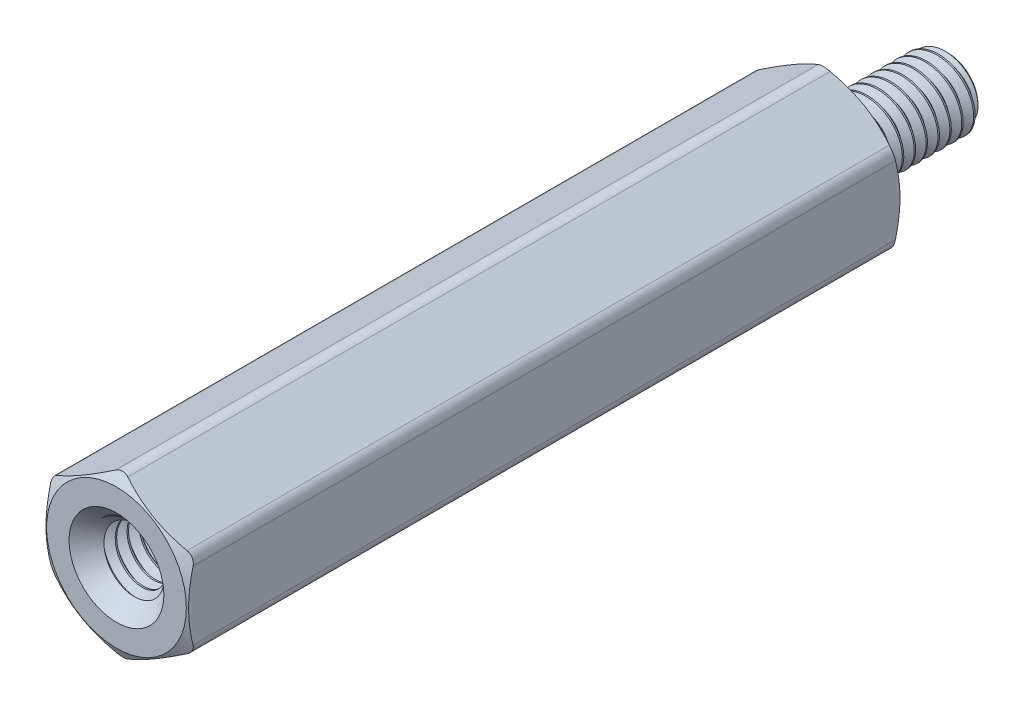
SolidWorks part; units mm, degrees
ref_plane "Front Plane" through (0, 0, 0) normal (0, 0, 1) x (1, 0, 0)
ref_plane "Top Plane" through (0, 0, 0) normal (0, 1, 0) x (1, 0, 0)
ref_plane "Right Plane" through (0, 0, 0) normal (1, 0, 0) x (0, 0, -1)
sketch "Sketch1" plane through (0, 0, 0) normal (0, 0, 1) x (1, 0, 0)
  line L1 (3, 1.7321) -> (0, 3.4641)
  line L2 (0, 3.4641) -> (-3, 1.7321)
  line L3 (-3, 1.7321) -> (-3, -1.7321)
  line L4 (-3, -1.7321) -> (0, -3.4641)
  line L5 (0, -3.4641) -> (3, -1.7321)
  line L6 (3, -1.7321) -> (3, 1.7321)
  circle A0 centre (0, 0) radius 3 construction
  point P10 (0, -3)
  dimension "Hex Size" = 6
sketch "Sketch2" plane through (0, 0, 0) normal (1, 0, 0) x (0, 0, -1)
  line L0 (5, 0) -> (-30, 0) construction
  line L2 (0, 1.5) -> (0, -1.5) construction
  line L3 (-23.6, 1.5) -> (-23.6, -1.5) construction
  line L4 (-30.4687, 1.5541) -> (-30.2187, 1.1211) construction
  line L5 (-30.2187, 1.1211) -> (-29.9687, 1.5541) construction
  line L6 (-29.9687, 1.5541) -> (-30.4687, 1.5541) construction
  line L7 (-30.4375, 1.5) -> (-30, 1.5) construction
  line L8 (-30.25, 1.1752) -> (-30.1875, 1.1752) construction
  line L9 (-30.2187, 1.1752) -> (-30.2187, 1.1211) construction
  line L10 (-30.2187, 1.5) -> (-30.2187, 1.5541) construction
  line L11 (4.9687, 1.5541) -> (5.4687, 1.5541) construction
  line L12 (5.4687, 1.5541) -> (5.2187, 1.1211) construction
  line L13 (5.2187, 1.1211) -> (4.9687, 1.5541) construction
  line L14 (5, 1.5) -> (5.4375, 1.5) construction
  line L15 (5.1875, 1.1752) -> (5.25, 1.1752) construction
  line L16 (5.2187, 1.1752) -> (5.2187, 1.1211) construction
  line L17 (5.2187, 1.5) -> (5.2187, 1.5541) construction
  line L18 (0, 3.4641) -> (-30, 3.4641) construction
  point P6 (0, 0)
  point P9 (-23.6, 0)
  dimension "Length" = 30
sketch "Sketch3" plane through (0, 0, 0) normal (1, 0, 0) x (0, 0, -1)
  line L0 (-23.6, 0) -> (5, 0)
  line L1 (-23.6, 1.5) -> (-23.6, -1.5) construction
  line L2 (5, 0) -> (5, 1.25)
  line L3 (5, 1.25) -> (4.75, 1.5)
  line L4 (4.75, 1.5) -> (0.7875, 1.5)
  line L5 (0.7875, 1.5) -> (0.6, 1.1752)
  line L6 (-23.6, 0) -> (-23.6, 1.25)
  line L7 (-23.6, 1.25) -> (-23.85, 1.5)
  line L8 (-23.85, 1.5) -> (-29.75, 1.5)
  line L9 (-29.75, 1.5) -> (-30, 1.75)
  line L10 (4.75, 0) -> (4.75, -1.5) construction
  line L11 (-30, 1.75) -> (-30, 3)
  line L12 (-30, 3) -> (0, 3)
  line L14 (0.6, 1.1752) -> (0.25, 1.1752)
  line L15 (0, 1.4252) -> (0, 3)
  arc A0 (0, 1.4252) -> (0.25, 1.1752) centre (0.25, 1.4252) ccw
  point P5 (-30, -3)
  point P8 (-28.75, -1.5)
  point P9 (3.75, -1.5)
  point P27 (0, 1.1752)
  dimension "D4" = 0.25
  dimension "D2" = 0.25
  dimension "D1" = 45
  dimension "D6" = 1.25
  dimension "D7" = 60
  dimension "D3" = 1.25
  dimension "D5" = 0.6
revolve "Revolve1" add sketch "Sketch3" angle 360 about L0 region at (0, 1.5183, 12.2524)
sketch "Sketch4" plane through (0, 0, 30) normal (0, 0, 1) x (1, 0, 0)
  line L0 (0, 3) -> (0, 1.5) construction
  line L1 (-3, 1.7321) -> (-3, -1.7321)
  line L2 (-3, -1.7321) -> (0, -3.4641)
  line L3 (0, -3.4641) -> (3, -1.7321)
  line L4 (3, -1.7321) -> (3, 1.7321)
  line L5 (3, 1.7321) -> (0, 3.4641)
  line L6 (0, 3.4641) -> (-3, 1.7321)
  circle A0 centre (0, 0) radius 3 construction
  circle A1 centre (0, 0) radius 2.25
  circle A2 centre (0, 0) radius 3 construction
  point P16 (0, 2.25)
extrude "Boss-Extrude1" add sketch "Sketch4" against normal up to surface (30 mm away) up to face at (0, 3, 0)
sketch "Sketch5" plane through (0, 0, 30) normal (0, 0, 1) x (1, 0, 0)
  line L0 (-0.8604, 1.2287) -> (0.8604, -1.2287) construction
  line L1 (0, 1.5) -> (0, -1.5) construction
  line L3 (0, -6.2062) -> (0, 6.2062) construction
  circle A0 centre (0, 0) radius 2.94
  point P11 (0.8604, -1.2287)
  dimension "D1" = 5.88
  dimension "D2" = 35
extrude "Cut-Extrude1" cut sketch "Sketch5" against normal through all draft 60 flip side to cut
sketch "Sketch6" plane through (0, 0, 0) normal (0, 0, -1) x (-1, 0, 0)
  circle A0 centre (0, 0) radius 2.94
  circle A1 centre (0, 0) radius 2.94 construction
extrude "Cut-Extrude2" cut sketch "Sketch6" against normal through all draft 60 flip side to cut
fillet "Fillet1" radius 0.51 6 edges at (0, 3.4641, 15) (-3, -1.7321, 15) (0, -3.4641, 15) (3, -1.7321, 15) (3, 1.7321, 15) (-3, 1.7321, 15)
sketch "Drawing1" plane through (0, 0, 0) normal (1, 0, 0) x (0, 0, -1)
  line L0 (-30, 1.5) -> (-23.6, 1.5) construction
  line L1 (-23.6, 1.5) -> (-23.6, -1.5) construction
  line L2 (-23.6, -1.5) -> (-30, -1.5) construction
sketch "Sketch7" plane through (0, 0, 0) normal (-1, 0, 0) x (0, 0, 1)
  line L0 (-5.1875, 1.1752) -> (-5.25, 1.1752)
  line L1 (-5.25, 1.1752) -> (-5.4531, 1.5271)
  line L2 (-5.4687, 1.5541) -> (-5.2187, 1.1211) construction
  line L3 (-5.4531, 1.5271) -> (-4.9844, 1.5271)
  line L4 (-5.2187, 1.1211) -> (-4.9687, 1.5541) construction
  line L5 (-4.9844, 1.5271) -> (-5.1875, 1.1752)
  line L6 (-5.2187, 1.5) -> (-5.2187, 1.5541) construction
  point P12 (-5.2187, 1.5271)
sketch "Sketch8" plane through (0, 0, -5) normal (0, 0, -1) x (-1, 0, 0)
  circle A0 centre (0, 0) radius 1.5
curve "Helix/Spiral1" pitch 0.5 height 4.85 radius 1.5 centre (0, 0, -5) axis (0, 0, 1) start towards (0, 1, 0)
sweep "Cut-Sweep1" cut profiles "Sketch7" path "Helix/Spiral1" align with end faces yes
sketch "Sketch9" plane through (0, 0, 23.6) normal (0, 0, 1) x (1, 0, 0)
  circle A0 centre (0, 0) radius 1.75
extrude "Boss-Extrude2" add sketch "Sketch9" along normal up to surface (6.4 mm away) up to face at (0, 1.75, 30)
sketch "Sketch10" plane through (0, 0, 0) normal (1, 0, 0) x (0, 0, -1)
  line L0 (5, 0) -> (-30, 0) construction
  line L1 (-23.6, 1.5) -> (-30, 1.5)
  line L2 (-23.6, 1.5) -> (-23.6, 0)
  line L3 (-23.6, 0) -> (-30, 0)
  line L4 (-30, 1.5) -> (-30, 0)
revolve "Revolve2" add sketch "Sketch10" angle 360 about L0
sketch "Sketch11" plane through (0, 0, 30) normal (0, 0, 1) x (1, 0, 0)
  circle A0 centre (0, 0) radius 1.5
  circle A1 centre (0, 0) radius 1.5 construction
sketch "Sketch12" plane through (0, 0, 0) normal (1, 0, 0) x (0, 0, -1)
  line L0 (-30.25, 1.1752) -> (-30.1875, 1.1752)
  line L1 (-30.1875, 1.1752) -> (-29.9844, 1.5271)
  line L2 (-30.2187, 1.1211) -> (-29.9687, 1.5541) construction
  line L3 (-29.9844, 1.5271) -> (-30.4531, 1.5271)
  line L4 (-30.4687, 1.5541) -> (-30.2187, 1.1211) construction
  line L5 (-30.4531, 1.5271) -> (-30.25, 1.1752)
  line L6 (-30.2187, 1.5) -> (-30.2187, 1.5541) construction
  point P12 (-30.2187, 1.5271)
curve "Helix/Spiral2" pitch 0.5 height 6.9 radius 1.5 centre (0, 0, 30) axis (0, 0, -1) start towards (0, 1, 0)
sweep "Cut-Sweep2" cut profiles "Sketch12" path "Helix/Spiral2" align with end faces yes
combine bodies "Combine1" operation type subtract main body 113 bodies to subtract 114
sketch "Sketch13" plane through (0, 0, 30) normal (0, 0, 1) x (1, 0, 0)
  circle A0 centre (0, 0) radius 1.995
  dimension "D1" = 3.99
extrude "Cut-Extrude3" cut sketch "Sketch13" against normal through all draft 45
equation "\"Thread Pitch (B)/8@Sketch2\" = \"Thread Pitch (B)@Sketch2\" / 8"
equation "\"Thread Pitch (A)/8@Sketch2\" = \"Thread Pitch (A)@Sketch2\" / 8"
equation "\"D1@Sketch5\"=\"Hex Size@Sketch1\" * .98"
equation "\"D1@Fillet1\"=\"Hex Size@Sketch1\" * .085"
equation "\"D2@Sketch3\"=\"Thread Pitch (A)@Sketch2\" * .5"
equation "\"D4@Sketch3\" = \"D2@Sketch3\""
equation "\"D6@Sketch3\" = \"Thread Pitch (A)@Sketch2\" * 2.5"
equation "\"D3@Helix/Spiral1\" = \"Thread Length (A)@Sketch2\" - \"D5@Sketch3\" * .25"
equation "\"D4@Helix/Spiral1\" = \"Thread Pitch (A)@Sketch2\""
equation "\"D3@Sketch3\" = \"Thread Pitch (B)@Sketch2\" * 2.5"
equation "\"D5@Sketch3\" = \"Thread Length (A)@Sketch2\" * .12"
equation "\"D3@Helix/Spiral2\" = \"Minimum Thread Length (B)@Sketch2\" + \"Thread Pitch (B)@Sketch2\""
equation "\"D4@Helix/Spiral2\" = \"Thread Pitch (B)@Sketch2\""
equation "\"D1@Sketch13\"=(\"Hex Size@Sketch1\"-\"Thread Size (A)@Sketch2\")*.33+\"Thread Size (A)@Sketch2\""
